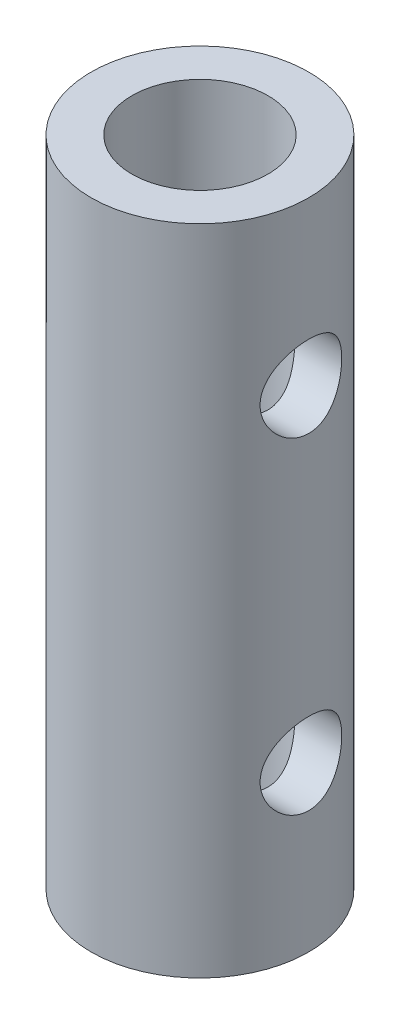
SolidWorks part; units mm, degrees
ref_plane "Front Plane" through (0, 0, 0) normal (0, 0, 1) x (1, 0, 0)
ref_plane "Top Plane" through (0, 0, 0) normal (0, 1, 0) x (1, 0, 0)
ref_plane "Right Plane" through (0, 0, 0) normal (1, 0, 0) x (0, 0, -1)
sketch "Sketch1" plane through (0, 0, 0) normal (0, 1, 0) x (1, 0, 0)
  circle A0 centre (0, 0) radius 4
  dimension "D1" = 8
extrude "Boss-Extrude1" add sketch "Sketch1" along normal blind 24
sketch "Sketch2" plane through (0, 24, 0) normal (0, 1, 0) x (1, 0, 0)
  circle A0 centre (0, 0) radius 2.5
  dimension "D1" = 5
extrude "Cut-Extrude1" cut sketch "Sketch2" against normal blind 11
sketch "Sketch3" plane through (0, 0, 0) normal (0, -1, 0) x (1, 0, 0)
  circle A0 centre (0, 0) radius 2.5
  dimension "D1" = 5
extrude "Cut-Extrude2" cut sketch "Sketch3" against normal blind 11
sketch "Sketch4" plane through (0, 0, 0) normal (1, 0, 0) x (0, 0, -1)
  line L0 (0, 24) -> (0, 0) construction
  line L1 (2.5, 24) -> (-2.5, 24) construction
  line L2 (-4, 12) -> (4, 12) construction
  line L3 (-4, 24) -> (-4, 0) construction
  line L4 (4, 0) -> (4, 24) construction
  circle A0 centre (0, 18) radius 1.5
  circle A1 centre (0, 6) radius 1.5
  dimension "D1" = 3
  dimension "D2" = 6
extrude "Cut-Extrude3" cut sketch "Sketch4" against normal blind 11 and the other way blind 11
